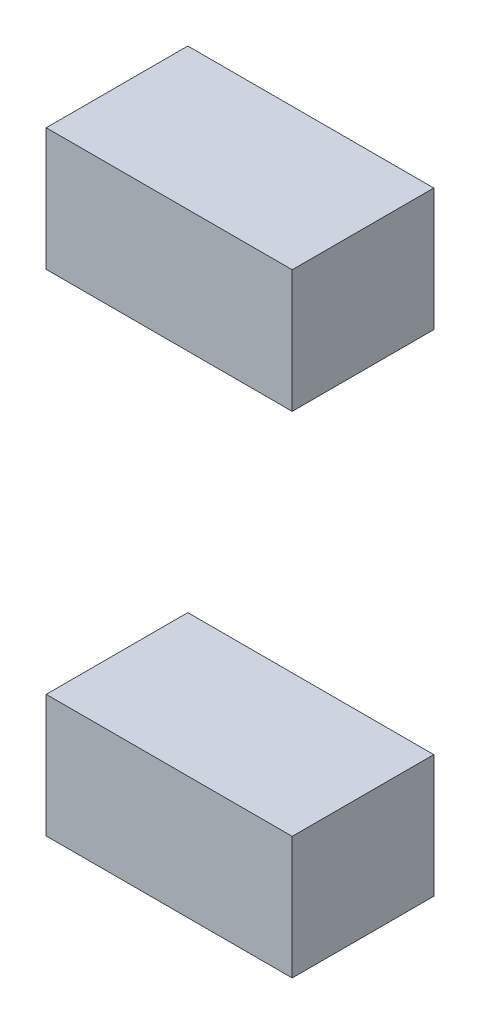
SolidWorks part; units mm, degrees
ref_plane "Front Plane" through (0, 0, 0) normal (0, 0, 1) x (1, 0, 0)
ref_plane "Top Plane" through (0, 0, 0) normal (0, 1, 0) x (1, 0, 0)
ref_plane "Right Plane" through (0, 0, 0) normal (1, 0, 0) x (0, 0, -1)
other "Center of Mass"
sketch "Sketch1" plane through (0, 0, 0) normal (0, 1, 0) x (1, 0, 0)
  line L1 (-52.3812, 23.9398) -> (47.8796, 23.9398)
  line L2 (-52.3812, 23.9398) -> (-52.3812, -33.7613)
  line L3 (-52.3812, -33.7613) -> (47.8796, -33.7613)
  line L4 (47.8796, 23.9398) -> (47.8796, -33.7613)
extrude "Boss-Extrude1" add sketch "Sketch1" along normal blind 50
ref_plane "Plane1" through (0, 200, 0) normal (0, 1, 0) x (1, 0, 0)
sketch "Sketch2" plane through (0, 200, 0) normal (0, 1, 0) x (1, 0, 0)
  line L1 (-52.3812, 23.9398) -> (47.8796, 23.9398)
  line L2 (-52.3812, 23.9398) -> (-52.3812, -33.7613)
  line L3 (-52.3812, -33.7613) -> (47.8796, -33.7613)
  line L4 (47.8796, 23.9398) -> (47.8796, -33.7613)
extrude "Boss-Extrude2" add sketch "Sketch2" along normal blind 50 separate body
ref_axis "Axis1" through (47.8796, 250, 33.7613) along (0, -1, 0)
ref_axis "Axis2" through (52.8927, 0, 0) along (-1, 0, 0)
ref_axis "Axis3" through (-52.3812, 50, 33.7613) along (0.4339, 0.8656, -0.2497)
sketch "Sketch3" plane through (0, 50, 0) normal (0, 1, 0) x (1, 0, 0)
  point P0 (-38.2548, 7.4834)
ref_axis "Axis4" through (-38.2548, 50, -7.4834) along (0, -1, 0)
ref_point "Point1"
